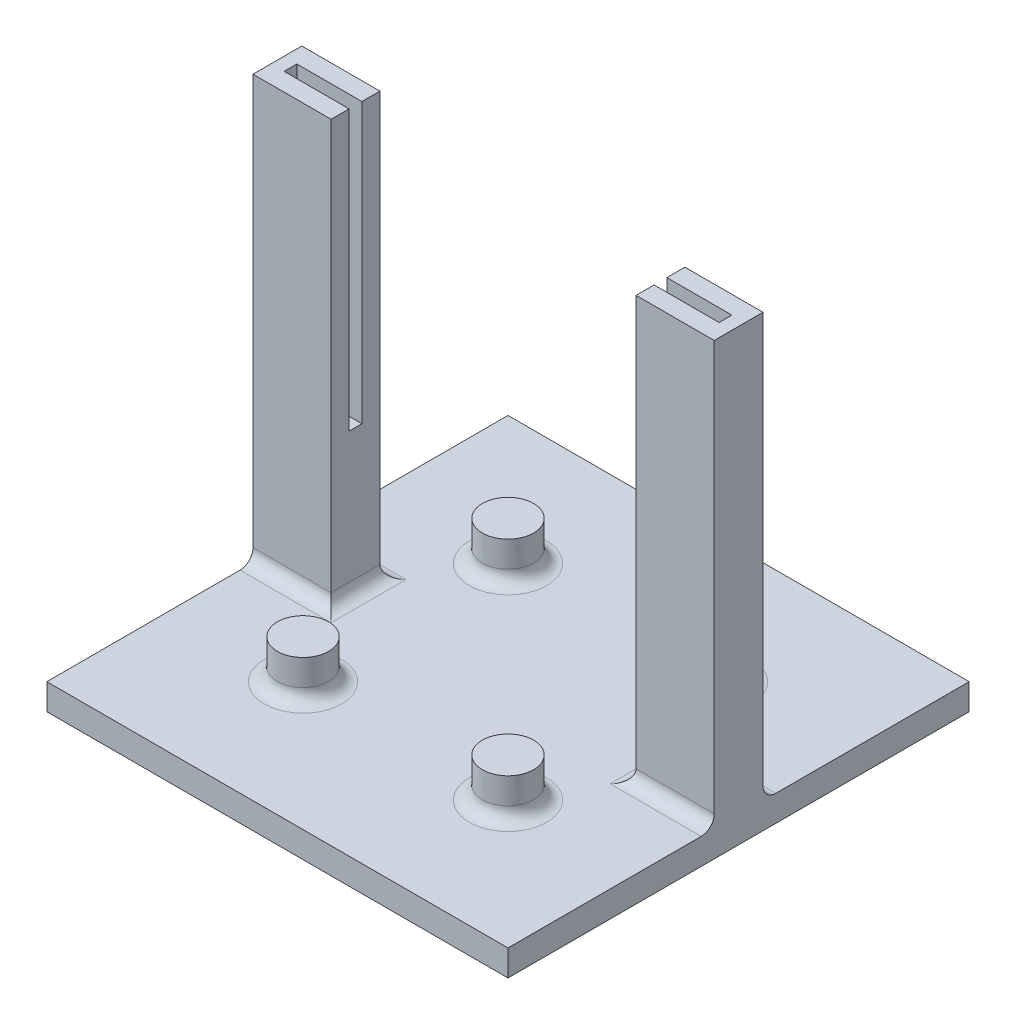
SolidWorks part; units mm, degrees
ref_plane "Front Plane" through (0, 0, 0) normal (0, 0, 1) x (1, 0, 0)
ref_plane "Top Plane" through (0, 0, 0) normal (0, 1, 0) x (1, 0, 0)
ref_plane "Right Plane" through (0, 0, 0) normal (1, 0, 0) x (0, 0, -1)
sketch "Sketch1" plane through (0, 0, 0) normal (0, 1, 0) x (1, 0, 0)
  line L1 (-13.0175, 13.0175) -> (13.0175, 13.0175) construction
  line L2 (-13.0175, 13.0175) -> (-13.0175, -13.0175) construction
  line L3 (-13.0175, -13.0175) -> (13.0175, -13.0175) construction
  line L4 (13.0175, 13.0175) -> (13.0175, -13.0175) construction
  line L5 (-13.0175, 13.0175) -> (13.0175, -13.0175) construction
  line L6 (-13.0175, -13.0175) -> (13.0175, 13.0175) construction
  line L7 (10, -10) -> (-10, -10) construction
  line L8 (10, -10) -> (10, 10) construction
  line L9 (10, 10) -> (-10, 10) construction
  line L10 (-10, -10) -> (-10, 10) construction
  line L11 (10, -10) -> (-10, 10) construction
  line L12 (10, 10) -> (-10, -10) construction
  line L13 (22.5, -22.5) -> (-22.5, -22.5)
  line L14 (22.5, -22.5) -> (22.5, 22.5)
  line L15 (22.5, 22.5) -> (-22.5, 22.5)
  line L16 (-22.5, -22.5) -> (-22.5, 22.5)
  line L17 (22.5, -22.5) -> (-22.5, 22.5) construction
  line L18 (22.5, 22.5) -> (-22.5, -22.5) construction
  point P0 (0, 0)
  point P6 (0, 0)
  point P11 (0, 0)
  dimension "D1" = 26.035
  dimension "D2" = 26.035
  dimension "D3" = 20
  dimension "D4" = 45
  dimension "D5" = 45
extrude "Boss-Extrude1" add sketch "Sketch1" against normal blind 2.54
sketch "Sketch2" plane through (0, 0, 0) normal (0, 1, 0) x (1, 0, 0)
  line L0 (0, 22.5) -> (0, -22.5) construction
  line L1 (22.5, 22.5) -> (-22.5, 22.5) construction
  line L2 (22.5, -22.5) -> (-22.5, -22.5) construction
  line L3 (-22.5, 0) -> (22.5, 0) construction
  line L4 (-22.5, -22.5) -> (-22.5, 22.5) construction
  line L5 (22.5, -22.5) -> (22.5, 22.5) construction
  circle A0 centre (-10, 10) radius 2.5
  circle A1 centre (10, 10) radius 2.5
  circle A2 centre (10, -10) radius 2.5
  circle A3 centre (-10, -10) radius 2.5
  dimension "D1" = 5
extrude "Boss-Extrude2" add sketch "Sketch2" along normal blind 3.81
sketch "Sketch3" plane through (0, 0, 0) normal (0, 1, 0) x (1, 0, 0)
  line L0 (-22.5, -22.5) -> (-22.5, 22.5) construction
  line L1 (-22.5, 2.3812) -> (-14.88, 2.3812)
  line L2 (-22.5, 2.3812) -> (-22.5, -2.3813)
  line L3 (-22.5, -2.3813) -> (-14.88, -2.3813)
  line L4 (-14.88, 2.3812) -> (-14.88, -2.3813)
  line L5 (-14.88, 0) -> (0, 0) construction
  line L6 (-13.0175, -13.0175) -> (13.0175, 13.0175) construction
  line L7 (0, 0) -> (0, 22.5) construction
  line L8 (22.5, 22.5) -> (-22.5, 22.5) construction
  line L9 (14.88, 2.3812) -> (14.88, -2.3813)
  line L10 (22.5, -2.3813) -> (14.88, -2.3813)
  line L11 (22.5, 2.3812) -> (22.5, -2.3813)
  line L12 (22.5, 2.3812) -> (14.88, 2.3812)
  dimension "D1" = 7.62
  dimension "D2" = 4.7625
extrude "Boss-Extrude3" add sketch "Sketch3" along normal blind 41.275
sketch "Sketch4" plane through (0, 41.275, 0) normal (0, 1, 0) x (1, 0, 0)
  line L0 (-22.5, 0) -> (-21.2217, 0) construction
  line L1 (-22.5, -22.5) -> (-22.5, 22.5) construction
  line L2 (21.2217, 0) -> (22.5, 0) construction
  line L3 (-21.2217, 0.6223) -> (21.2217, 0.6223)
  line L4 (-21.2217, 0.6223) -> (-21.2217, -0.6223)
  line L5 (-21.2217, -0.6223) -> (21.2217, -0.6223)
  line L6 (21.2217, 0.6223) -> (21.2217, -0.6223)
  line L7 (22.5, -22.5) -> (22.5, 22.5) construction
  dimension "D1" = 42.4434
  dimension "D2" = 1.2446
extrude "Cut-Extrude1" cut sketch "Sketch4" against normal blind 27.2288
fillet "Fillet1" radius 1.27 10 edges at (-10, 0, -7.5) (10, 0, -12.5) (10, 0, 12.5) (-10, 0, 7.5) (14.88, 0, 0) (18.69, 0, -2.3812) (18.69, 0, 2.3813) (-18.69, 0, -2.3812) (-18.69, 0, 2.3813) (-14.88, 0, 0)
